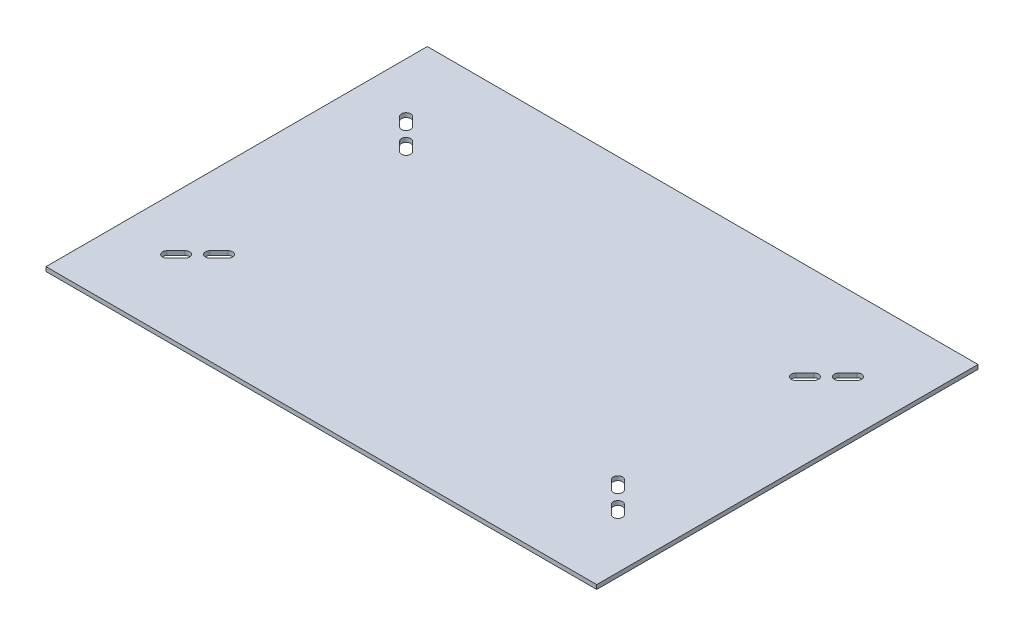
SolidWorks part; units mm, degrees
ref_plane "Front Plane" through (0, 0, 0) normal (0, 0, 1) x (1, 0, 0)
ref_plane "Top Plane" through (0, 0, 0) normal (0, 1, 0) x (1, 0, 0)
ref_plane "Right Plane" through (0, 0, 0) normal (1, 0, 0) x (0, 0, -1)
sketch "Sketch1" plane through (0, 0, 0) normal (0, 1, 0) x (1, 0, 0)
  line L1 (0, 0) -> (330.2, 0)
  line L2 (0, 0) -> (0, -228.6)
  line L3 (0, -228.6) -> (330.2, -228.6)
  line L4 (330.2, 0) -> (330.2, -228.6)
  dimension "D1" = 330.2
  dimension "D2" = 228.6
extrude "base plate" add sketch "Sketch1" against normal blind 2.54
sketch "center lines" plane through (0, 0, 0) normal (0, 1, 0) x (1, 0, 0)
  line L0 (165.1, 0) -> (165.1, -228.6) construction
  line L1 (330.2, 0) -> (0, 0) construction
  line L2 (0, -228.6) -> (330.2, -228.6) construction
  line L3 (0, -114.3) -> (330.2, -114.3) construction
  line L4 (0, 0) -> (0, -228.6) construction
  line L5 (330.2, -228.6) -> (330.2, 0) construction
sketch "Sketch3" plane through (0, 0, 0) normal (0, 1, 0) x (1, 0, 0)
  line L0 (21.0672, -185.8525) -> (30.0475, -194.8328)
  line L1 (30.0475, -194.8328) -> (60.5804, -164.2999)
  line L2 (60.5804, -164.2999) -> (51.6001, -155.3196)
  line L3 (51.6001, -155.3196) -> (21.0672, -185.8525)
  line L4 (29.9612, -185.9388) -> (35.3494, -180.5506) construction
  line L5 (28.0167, -183.9942) -> (33.4048, -178.6061)
  line L6 (31.9058, -187.8833) -> (37.2939, -182.4952)
  line L7 (0, -228.6) -> (330.2, -228.6) construction
  line L8 (48.2187, -167.6813) -> (42.8306, -173.0694) construction
  line L9 (50.1633, -169.6258) -> (44.7751, -175.014)
  line L10 (165.1, 0) -> (165.1, -228.6) construction
  line L11 (0, -114.3) -> (330.2, -114.3) construction
  line L12 (60.5804, -64.3001) -> (51.6001, -73.2804)
  line L13 (30.0475, -33.7672) -> (60.5804, -64.3001)
  line L14 (21.0672, -42.7475) -> (30.0475, -33.7672)
  line L15 (51.6001, -73.2804) -> (21.0672, -42.7475)
  line L16 (300.1525, -33.7672) -> (269.6196, -64.3001)
  line L17 (309.1328, -42.7475) -> (300.1525, -33.7672)
  line L18 (278.5999, -73.2804) -> (309.1328, -42.7475)
  line L19 (269.6196, -64.3001) -> (278.5999, -73.2804)
  line L20 (269.6196, -164.2999) -> (278.5999, -155.3196)
  line L21 (300.1525, -194.8328) -> (269.6196, -164.2999)
  line L22 (309.1328, -185.8525) -> (300.1525, -194.8328)
  line L23 (278.5999, -155.3196) -> (309.1328, -185.8525)
  line L24 (46.2742, -165.7367) -> (40.886, -171.1249)
  line L25 (29.9612, -42.6612) -> (35.3494, -48.0494) construction
  line L26 (28.0167, -44.6058) -> (33.4048, -49.9939)
  line L27 (31.9058, -40.7167) -> (37.2939, -46.1048)
  line L28 (48.2187, -60.9187) -> (42.8306, -55.5306) construction
  line L29 (50.1633, -58.9742) -> (44.7751, -53.586)
  line L30 (46.2742, -62.8633) -> (40.886, -57.4751)
  line L31 (300.2388, -42.6612) -> (294.8506, -48.0494) construction
  line L32 (302.1833, -44.6058) -> (296.7952, -49.9939)
  line L33 (298.2942, -40.7167) -> (292.9061, -46.1048)
  line L34 (281.9813, -60.9187) -> (287.3694, -55.5306) construction
  line L35 (280.0367, -58.9742) -> (285.4249, -53.586)
  line L36 (283.9258, -62.8633) -> (289.314, -57.4751)
  line L37 (281.9813, -167.6813) -> (287.3694, -173.0694) construction
  line L38 (280.0367, -169.6258) -> (285.4249, -175.014)
  line L39 (283.9258, -165.7367) -> (289.314, -171.1249)
  line L40 (300.2388, -185.9388) -> (294.8506, -180.5506) construction
  line L41 (302.1833, -183.9942) -> (296.7952, -178.6061)
  line L42 (298.2942, -187.8833) -> (292.9061, -182.4952)
  line L43 (51.6001, -164.2999) -> (51.6001, -155.3196)
  line L44 (60.5804, -164.2999) -> (51.6001, -164.2999)
  line L45 (51.6001, -64.3001) -> (51.6001, -73.2804)
  line L46 (60.5804, -64.3001) -> (51.6001, -64.3001)
  line L47 (278.5999, -64.3001) -> (278.5999, -73.2804)
  line L48 (269.6196, -64.3001) -> (278.5999, -64.3001)
  line L49 (278.5999, -164.2999) -> (278.5999, -155.3196)
  line L50 (269.6196, -164.2999) -> (278.5999, -164.2999)
  arc A0 (28.0167, -183.9942) -> (31.9058, -187.8833) centre (29.9612, -185.9388) ccw
  arc A1 (37.2939, -182.4952) -> (33.4048, -178.6061) centre (35.3494, -180.5506) ccw
  arc A2 (50.1633, -169.6258) -> (46.2742, -165.7367) centre (48.2187, -167.6813) ccw
  arc A3 (40.886, -171.1249) -> (44.7751, -175.014) centre (42.8306, -173.0694) ccw
  arc A4 (28.0167, -44.6058) -> (31.9058, -40.7167) centre (29.9612, -42.6612) cw
  arc A5 (37.2939, -46.1048) -> (33.4048, -49.9939) centre (35.3494, -48.0494) cw
  arc A6 (50.1633, -58.9742) -> (46.2742, -62.8633) centre (48.2187, -60.9187) cw
  arc A7 (40.886, -57.4751) -> (44.7751, -53.586) centre (42.8306, -55.5306) cw
  arc A8 (302.1833, -44.6058) -> (298.2942, -40.7167) centre (300.2388, -42.6612) ccw
  arc A9 (292.9061, -46.1048) -> (296.7952, -49.9939) centre (294.8506, -48.0494) ccw
  arc A10 (280.0367, -58.9742) -> (283.9258, -62.8633) centre (281.9813, -60.9187) ccw
  arc A11 (289.314, -57.4751) -> (285.4249, -53.586) centre (287.3694, -55.5306) ccw
  arc A12 (280.0367, -169.6258) -> (283.9258, -165.7367) centre (281.9813, -167.6813) cw
  arc A13 (289.314, -171.1249) -> (285.4249, -175.014) centre (287.3694, -173.0694) cw
  arc A14 (302.1833, -183.9942) -> (298.2942, -187.8833) centre (300.2388, -185.9388) cw
  arc A15 (292.9061, -182.4952) -> (296.7952, -178.6061) centre (294.8506, -180.5506) cw
  point P29 (32.6553, -183.2447)
  point P36 (45.5246, -170.3754)
  point P44 (32.6553, -45.3553)
  point P51 (45.5246, -58.2246)
  point P58 (297.5447, -45.3553)
  point P65 (284.6754, -58.2246)
  point P72 (284.6754, -170.3754)
  point P79 (297.5447, -183.2447)
  point P84 (37.2939, -178.6061)
  point P85 (40.886, -175.014)
  dimension "D6" = 2.75
  dimension "D10" = 5.08
  dimension "D9" = 2.032
  dimension "D1" = 43.18
  dimension "D2" = 12.7
  dimension "D3" = 45
  dimension "D4" = 99.9998
  dimension "D5" = 226.9998
  dimension "D7" = 7.62
  dimension "D8" = 6.35
extrude "Cut-Extrude9" cut sketch "Sketch3" against normal through all contours A5 L27 A4 L26 | L33 A9 L32 A8 | L36 A11 L35 A10 | A13 L39 A12 L38 | A15 L42 A14 L41 | L6 A1 L5 A0 | L24 A3 L9 A2 | L30 A7 L29 A6 region at (32.6553, 0, 45.3553) region at (297.5447, 0, 45.3553) region at (284.6754, 0, 58.2246) region at (284.6754, 0, 170.3754) region at (297.5447, 0, 183.2447)
